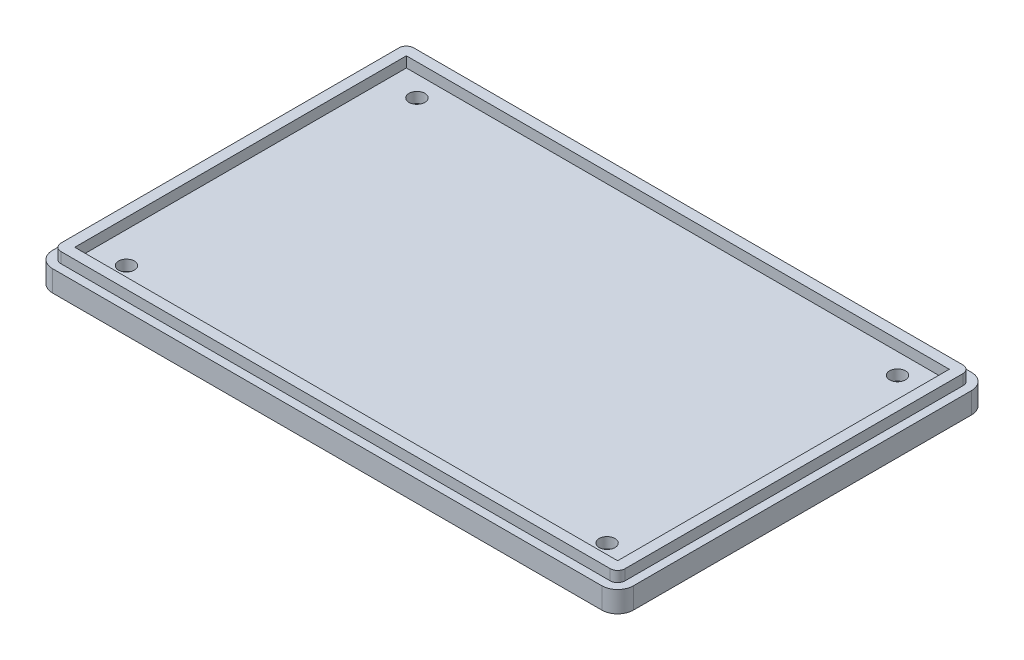
SolidWorks part; units mm, degrees
ref_plane "Front Plane" through (0, 0, 0) normal (0, 0, 1) x (1, 0, 0)
ref_plane "Top Plane" through (0, 0, 0) normal (0, 1, 0) x (1, 0, 0)
ref_plane "Right Plane" through (0, 0, 0) normal (1, 0, 0) x (0, 0, -1)
sketch "Sketch1" plane through (0, 0, 0) normal (0, 1, 0) x (1, 0, 0)
  line L1 (-52, -35) -> (52, -35)
  line L2 (-55, -32) -> (-55, 32)
  line L3 (-52, 35) -> (52, 35)
  line L4 (55, -32) -> (55, 32)
  line L5 (-55, -35) -> (55, 35) construction
  line L6 (-55, 35) -> (55, -35) construction
  line L10 (-53.4, -32) -> (-53.4, 32)
  line L11 (-52, 33.4) -> (52, 33.4)
  line L12 (53.4, -32) -> (53.4, 32)
  line L13 (-52, -33.4) -> (52, -33.4)
  line L14 (-51.4, -31.4) -> (-51.4, 31.4)
  line L15 (-51.4, 31.4) -> (51.4, 31.4)
  line L16 (51.4, -31.4) -> (51.4, 31.4)
  line L17 (-51.4, -31.4) -> (51.4, -31.4)
  arc A0 (-52, -35) -> (-55, -32) centre (-52, -32) cw
  arc A1 (52, -35) -> (55, -32) centre (52, -32) ccw
  arc A2 (52, 35) -> (55, 32) centre (52, 32) cw
  arc A3 (-55, 32) -> (-52, 35) centre (-52, 32) cw
  arc A4 (-53.4, 32) -> (-52, 33.4) centre (-52, 32) cw
  arc A5 (52, 33.4) -> (53.4, 32) centre (52, 32) cw
  arc A6 (52, -33.4) -> (53.4, -32) centre (52, -32) ccw
  arc A7 (-52, -33.4) -> (-53.4, -32) centre (-52, -32) cw
  arc A8 (-51.4, 31.4) -> (-51.4, 31.4) centre (-51.4, 31.4) cw
  arc A9 (51.4, 31.4) -> (51.4, 31.4) centre (51.4, 31.4) cw
  arc A10 (51.4, -31.4) -> (51.4, -31.4) centre (51.4, -31.4) ccw
  arc A11 (-51.4, -31.4) -> (-51.4, -31.4) centre (-51.4, -31.4) cw
  point P0 (0, 0)
  dimension "D4" = 3
  dimension "D1" = 110
  dimension "D2" = 70
  dimension "D3" = 1.6
  dimension "D5" = 2
extrude "Boss-Extrude1" add sketch "Sketch1" along normal blind 4 contours L1 A1 L4 A2 L3 A3 L2 A0
extrude "Boss-Extrude2" add sketch "Sketch1<3>" along normal blind 2 from surface contours L10 region at (-52.1403, 0, 0) starting at face at (0, 4, 0)
sketch "Sketch1<3>" plane through (0, 0, 0) normal (0, 1, 0) x (1, 0, 0) same geometry as "Sketch1"
sketch "Sketch2" plane through (0, 0, 0) normal (0, -1, 0) x (1, 0, 0)
  line L0 (-52, 35) -> (52, 35) construction
  line L1 (-45.5, 27.5) -> (45.5, 27.5) construction
  line L2 (-45.5, 27.5) -> (-45.5, -27.5) construction
  line L3 (-45.5, -27.5) -> (45.5, -27.5) construction
  line L4 (45.5, 27.5) -> (45.5, -27.5) construction
  line L5 (-55, 32) -> (-55, -32) construction
  line L6 (55, 32) -> (55, -32) construction
  line L7 (-52, -35) -> (52, -35) construction
  circle A0 centre (-45.5, 27.5) radius 1.5
  circle A1 centre (45.5, 27.5) radius 1.5
  circle A2 centre (45.5, -27.5) radius 1.5
  circle A3 centre (-45.5, -27.5) radius 1.5
  circle A4 centre (-45.5, 27.5) radius 3
  circle A5 centre (45.5, 27.5) radius 3
  circle A6 centre (45.5, -27.5) radius 3
  circle A7 centre (-45.5, -27.5) radius 3
  dimension "D5" = 3
  dimension "D6" = 6
  dimension "D1" = 7.5
  dimension "D2" = 9.5
  dimension "D3" = 9.5
  dimension "D4" = 7.5
extrude "Cut-Extrude1" cut sketch "Sketch2" against normal through all contours A0 | A1 | A2 | A3 region at (-45.5, 0, 27.5) region at (45.5, 0, 27.5) region at (45.5, 0, -27.5) region at (-45.5, 0, -27.5)
extrude "Cut-Extrude2" cut sketch "Sketch2<3>" against normal blind 2 contours A4 | A7 | A6 | A5
sketch "Sketch2<3>" plane through (0, 0, 0) normal (0, -1, 0) x (1, 0, 0) same geometry as "Sketch2"
